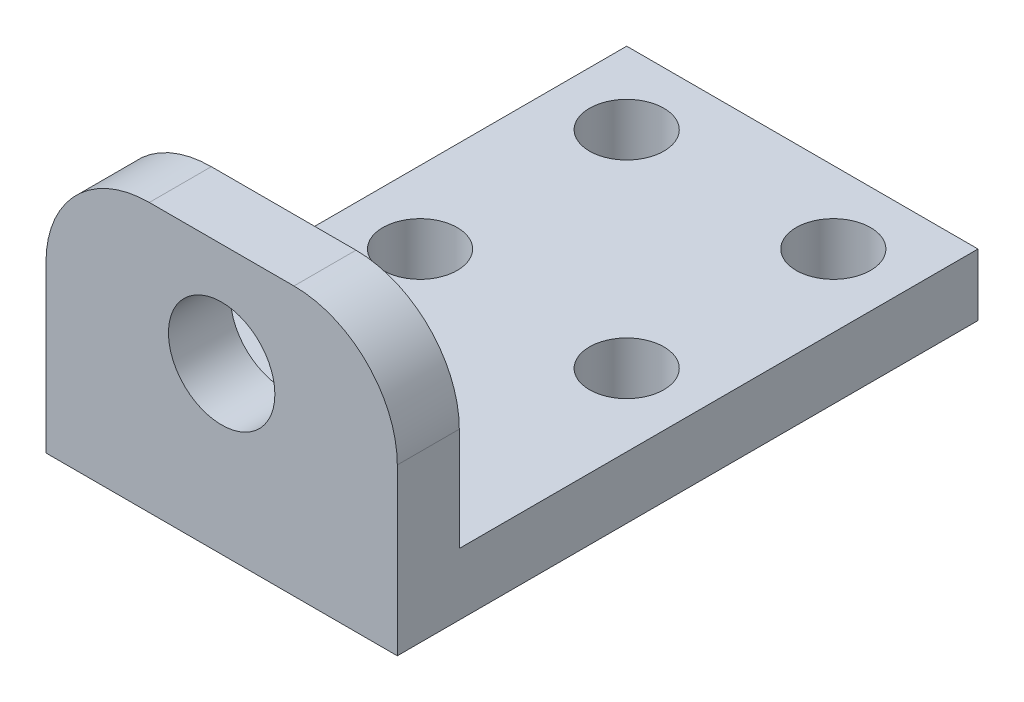
SolidWorks part; units mm, degrees
ref_plane "Front Plane" through (0, 0, 0) normal (0, 0, 1) x (1, 0, 0)
ref_plane "Top Plane" through (0, 0, 0) normal (0, 1, 0) x (1, 0, 0)
ref_plane "Right Plane" through (0, 0, 0) normal (1, 0, 0) x (0, 0, -1)
sketch "Sketch1" plane through (0, 0, 0) normal (1, 0, 0) x (0, 0, -1)
  line L0 (0, 0) -> (28.1, 0)
  line L1 (28.1, 0) -> (28.1, 3)
  line L2 (28.1, 3) -> (3, 3)
  line L3 (3, 3) -> (3, 13)
  line L4 (3, 13) -> (0, 13)
  line L5 (0, 13) -> (0, 0)
  dimension "D1" = 3
  dimension "D2" = 13
  dimension "D3" = 28.1
extrude "Boss-Extrude1" add sketch "Sketch1" along normal blind 17
sketch "Sketch2" plane through (0, 0, 0) normal (0, 0, 1) x (1, 0, 0)
  line L0 (0, 0) -> (17, 0) construction
  line L2 (8.5, 0) -> (8.5, 8) construction
  line L3 (17, 13) -> (0, 13) construction
  point P7 (8.5, 8)
  point P13 (8.5, 8)
  dimension "D1" = 5
hole_wizard "Ø5.0mm Dowel Hole1" positions "Sketch2" profile "Sketch3" hole size "Ø5.0" standard "ANSI Metric"
sketch "Sketch3" plane through (8.5, 8, 0) normal (1, 0, 0) x (0, -1, 0)
  line L0 (0, 0) -> (0, 4.5472)
  line L1 (0, 4.5472) -> (2.575, 3)
  line L2 (2.575, 3) -> (2.575, 0)
  line L5 (2.575, 0) -> (0, 0)
  line L10 (0, 4.5472) -> (-2.575, 3) construction
  line L11 (0, -6.35) -> (0, 107.95) construction
  dimension "Hole Dia." = 5.15
  dimension "Hole Depth" = 3
  dimension "Drill Angle" = 118
fillet "Fillet1" radius 5 2 edges at (0, 13, -1.5) (17, 13, -1.5)
sketch "Sketch4" plane through (0, 3, 0) normal (0, 1, 0) x (1, 0, 0)
  line L0 (8.5, 28.1) -> (8.5, 3) construction
  line L1 (17, 28.1) -> (0, 28.1) construction
  line L2 (17, 3) -> (0, 3) construction
  line L4 (17, 19.6) -> (0, 19.6) construction
  line L7 (0, 28.1) -> (0, 3) construction
  line L8 (17, 28.1) -> (17, 3) construction
  point P42 (3.5, 24.6)
  point P45 (3.5, 14.6)
  point P46 (13.5, 14.6)
  point P47 (13.5, 24.6)
  dimension "D1" = 5
  dimension "D2" = 5
  dimension "D3" = 8.5
hole_wizard "M3 Clearance Hole1" positions "Sketch4" profile "Sketch5" hole size "M3" standard "ANSI Metric" end condition through all
sketch "Sketch5" plane through (13.5, 3, -24.6) normal (1, 0, 0) x (0, 0, 1)
  line L0 (0, 0) -> (0, 3)
  line L1 (0, 3) -> (1.8, 3)
  line L2 (1.8, 3) -> (1.8, 0)
  line L5 (1.8, 0) -> (0, 0)
  line L11 (0, -6.35) -> (0, 107.95) construction
  dimension "Thru Hole Dia." = 3.6
  dimension "Thru Hole Depth" = 3
equation "\"Length\" = 31.1 - 3"
equation "\"D3@Sketch1\"=\"Length\""
